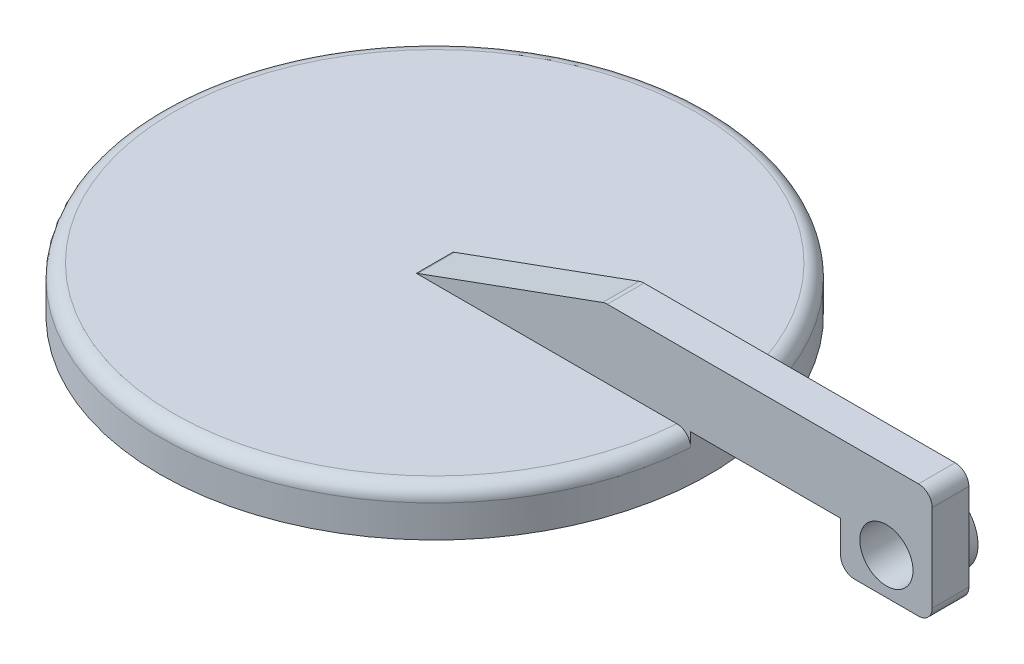
SolidWorks part; units mm, degrees
ref_plane "Front Plane" through (0, 0, 0) normal (0, 0, 1) x (1, 0, 0)
ref_plane "Top Plane" through (0, 0, 0) normal (0, 1, 0) x (1, 0, 0)
ref_plane "Right Plane" through (0, 0, 0) normal (1, 0, 0) x (0, 0, -1)
sketch "Sketch2" plane through (0, 0, 0) normal (0, 0, 1) x (1, 0, 0)
  line L7 (0, 0) -> (30, 0)
  line L8 (0, 0) -> (0, 5)
  line L9 (0, 5) -> (30, 5)
  line L10 (30, 0) -> (30, 5)
  dimension "D1" = 5
  dimension "D2" = 30
revolve "Revolve1" add sketch "Sketch2" angle 360 about L8
sketch "Sketch3" plane through (0, 5, 0) normal (0, 1, 0) x (1, 0, 0)
  line L0 (0, -10) -> (0, 10) construction
  line L1 (0, 10) -> (35, 10)
  line L2 (35, 10) -> (35, 6)
  line L3 (35, 6) -> (0, 6)
  line L4 (0, 10) -> (0, 6)
  line L5 (0, -10) -> (35, -10)
  line L6 (35, -10) -> (35, -6)
  line L7 (35, -6) -> (0, -6)
  line L8 (0, -6) -> (0, -10)
  line L9 (0, 2) -> (0, -2)
  line L10 (0, 2) -> (56.3, 2)
  line L11 (0, -2) -> (56.3, -2)
  line L12 (56.3, -2) -> (56.3, 2)
  point P4 (0, 0)
  point P13 (0, 0)
  circle M1 centre (0, 0) radius 30
  dimension "D1" = 20
  dimension "D2" = 35
  dimension "D3" = 4
  dimension "D4" = 4
  dimension "D5" = 56.3
extrude "Boss-Extrude1" add sketch "Sketch3" along normal blind 7.5 contours L9 L11 L10 M1 | L11 L12 L10 M1 region at (14.9889, 5, 0) region at (43.1389, 5, 0)
sketch "Sketch4" plane through (0, 0, 0) normal (0, 0, 1) x (1, 0, 0)
  line L5 (35, 8.75) -> (37.8, 8.75) construction
  line L7 (56.3, 8.75) -> (37.8, 8.75) construction
  line L8 (56.3, 12.5) -> (56.3, 5) construction
  line L10 (-0.0334, 5) -> (20.5727, 12.5)
  line L11 (29.9333, 5) -> (-30, 5) construction
  line L12 (0, 12.5) -> (56.3, 12.5) construction
  line L13 (0, 5) -> (29.9333, 5) construction
  line L14 (20.5727, 12.5) -> (0, 12.5)
  line L15 (0, 12.5) -> (-0.0334, 5)
  circle A0 centre (37.8, 8.75) radius 2
  dimension "D3" = 4
  dimension "D1" = 20
  dimension "D2" = 18.5
extrude "Cut-Extrude1" cut sketch "Sketch4" against normal mid plane 30 contours L14 L15 L10
sketch "Sketch6" plane through (0, 5, 0) normal (0, -1, 0) x (1, 0, 0)
  line L6 (56.3, 2) -> (46.3, 2)
  line L7 (56.3, 2) -> (56.3, -2) construction
  line L8 (29.9333, 2) -> (56.3, 2) construction
  line L9 (46.3, 2) -> (46.3, -2)
  line L10 (29.9333, -2) -> (56.3, -2) construction
  line L11 (46.3, -2) -> (56.3, -2)
  line L12 (56.3, -2) -> (56.3, 2)
  dimension "D1" = 10
extrude "Boss-Extrude2" add sketch "Sketch6" along normal blind 5
sketch "Sketch7" plane through (0, 0, 2) normal (0, 0, 1) x (1, 0, 0)
  line L0 (51.3, 4) -> (51.3, 0) construction
  line L2 (56.3, 0) -> (46.3, 0) construction
  circle A0 centre (51.3, 4) radius 2.9
  dimension "D2" = 5.8
  dimension "D1" = 4
extrude "Cut-Extrude2" cut sketch "Sketch7" against normal blind 10
fillet "Fillet2" radius 1.5 6 edges at (46.3, 0, 0) (56.3, 0, 0) (56.3, 12.5, 0) (20.5727, 12.5, 0) (0, 5.0121, 0) (-30, 5, 0)
sketch "Sketch9" plane through (0, 0, -2) normal (0, 0, -1) x (-1, 0, 0)
  circle A0 centre (-51.3, 4) radius 2.9
  circle A1 centre (-51.3, 4) radius 4
  dimension "D1" = 5.8
  dimension "D2" = 8
extrude "Boss-Extrude3" add sketch "Sketch9" along normal blind 2
